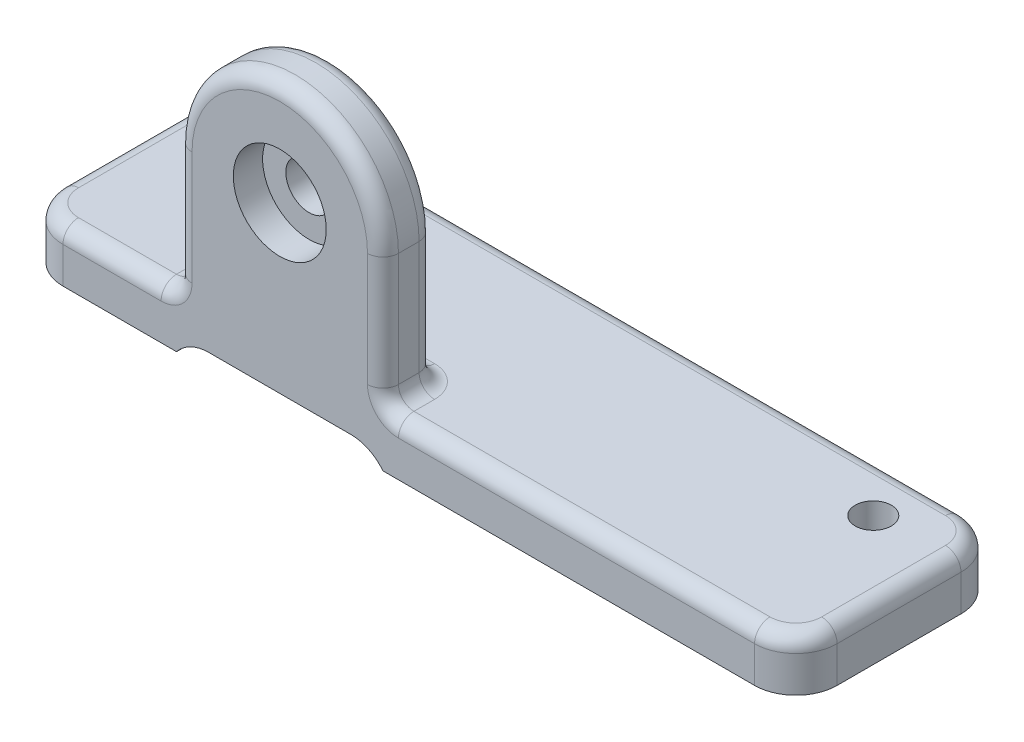
SolidWorks part; units mm, degrees
ref_plane "前基準面" through (0, 0, 0) normal (0, 0, 1) x (1, 0, 0)
ref_plane "上基準面" through (0, 0, 0) normal (0, 1, 0) x (1, 0, 0)
ref_plane "右基準面" through (0, 0, 0) normal (1, 0, 0) x (0, 0, -1)
sketch "草圖1" plane through (0, 0, 0) normal (0, 1, 0) x (1, 0, 0)
  line L1 (0, 0) -> (150, 0)
  line L2 (0, 0) -> (0, 40)
  line L3 (0, 40) -> (150, 40)
  line L4 (150, 0) -> (150, 40)
  dimension "D1" = 150
  dimension "D2" = 40
extrude "BasePlate" add sketch "草圖1" along normal blind 10
sketch "草圖2" plane through (0, 0, 0) normal (0, 0, 1) x (1, 0, 0)
  line L0 (30, 0) -> (30, 35)
  line L1 (0, 0) -> (150, 0) construction
  line L2 (70, 35) -> (70, 0)
  line L3 (70, 0) -> (30, 0)
  line L4 (0, 10) -> (0, 0) construction
  arc A0 (30, 35) -> (70, 35) centre (50, 35) cw
  dimension "D1" = 20
  dimension "D2" = 50
  dimension "D3" = 35
extrude "VertBoss" add sketch "草圖2" against normal blind 10
sketch "草圖3" plane through (0, 0, 0) normal (0, 0, 1) x (1, 0, 0)
  line L0 (0, 0) -> (150, 0) construction
  line L1 (30, 0) -> (70, 0)
  line L2 (30, 0) -> (30, 3)
  line L3 (30, 3) -> (70, 3)
  line L4 (70, 0) -> (70, 3)
  line L5 (30, 35) -> (30, 10) construction
  line L6 (70, 10) -> (70, 35) construction
  dimension "D1" = 3
extrude "BottomSolt" cut sketch "草圖3" against normal through all
hole_wizard "M8 六角頭螺栓的柱孔1" positions "草圖4" profile "草圖5" counterbore size "M8" standard "Ansi Metric" end condition through all
sketch "草圖4" plane through (0, 0, 0) normal (0, 0, 1) x (1, 0, 0)
  point P4 (50, 35)
sketch "草圖5" plane through (50, 35, 0) normal (1, 0, 0) x (0, -1, 0)
  line L0 (0, 0) -> (0, 40)
  line L1 (0, 40) -> (4.5, 40)
  line L3 (4.5, 40) -> (4.5, 5.68)
  line L4 (4.5, 5.68) -> (9.005, 5.68)
  line L5 (9.005, 5.68) -> (9.005, 0)
  line L7 (9.005, 0) -> (0, 0)
  line L11 (0, -6.35) -> (0, 107.95) construction
  dimension "貫穿孔直徑" = 9
  dimension "貫穿孔深度" = 40
  dimension "柱孔直徑" = 18.01
  dimension "柱孔深度" = 5.68
hole_wizard "Ø7.0 (7) 直徑孔1" positions "草圖6" profile "草圖8" hole size "Ø7.0" standard "Ansi Metric" end condition through all
sketch "草圖6" plane through (0, 10, 0) normal (0, 1, 0) x (1, 0, 0)
  line L0 (150, 0) -> (150, 40) construction
  line L1 (0, 40) -> (0, 0) construction
  line L2 (150, 40) -> (0, 40) construction
  point P0 (15, 30)
  point P2 (135, 30)
  dimension "D1" = 15
  dimension "D2" = 15
  dimension "D3" = 10
  dimension "D4" = 10
sketch "草圖8" plane through (15, 10, -30) normal (1, 0, 0) x (0, 0, 1)
  line L0 (0, 0) -> (0, 10)
  line L1 (0, 10) -> (3.5, 10)
  line L2 (3.5, 10) -> (3.5, 0)
  line L5 (3.5, 0) -> (0, 0)
  line L11 (0, -6.35) -> (0, 107.95) construction
  dimension "貫穿孔直徑" = 7
  dimension "貫穿孔深度" = 10
fillet "圓角1" radius 8 6 edges at (0, 5, 0) (0, 5, -40) (150, 5, 0) (150, 5, -40) (70, 3, -20) (30, 3, -20)
fillet "圓角2" radius 3 18 edges at (30, 22.5, -10) (50, 55, -10) (30, 22.5, 0) (50, 55, 0) (70, 22.5, -10) (70, 22.5, 0) (2.3431, 10, -37.6569) (0, 10, -20) (75, 10, -40) (2.3431, 10, -2.3431) (147.6569, 10, -37.6569) (19, 10, 0) (150, 10, -20) (30, 10, -5) (147.6569, 10, -2.3431) (50, 10, -10) (106, 10, 0) (70, 10, -5)
